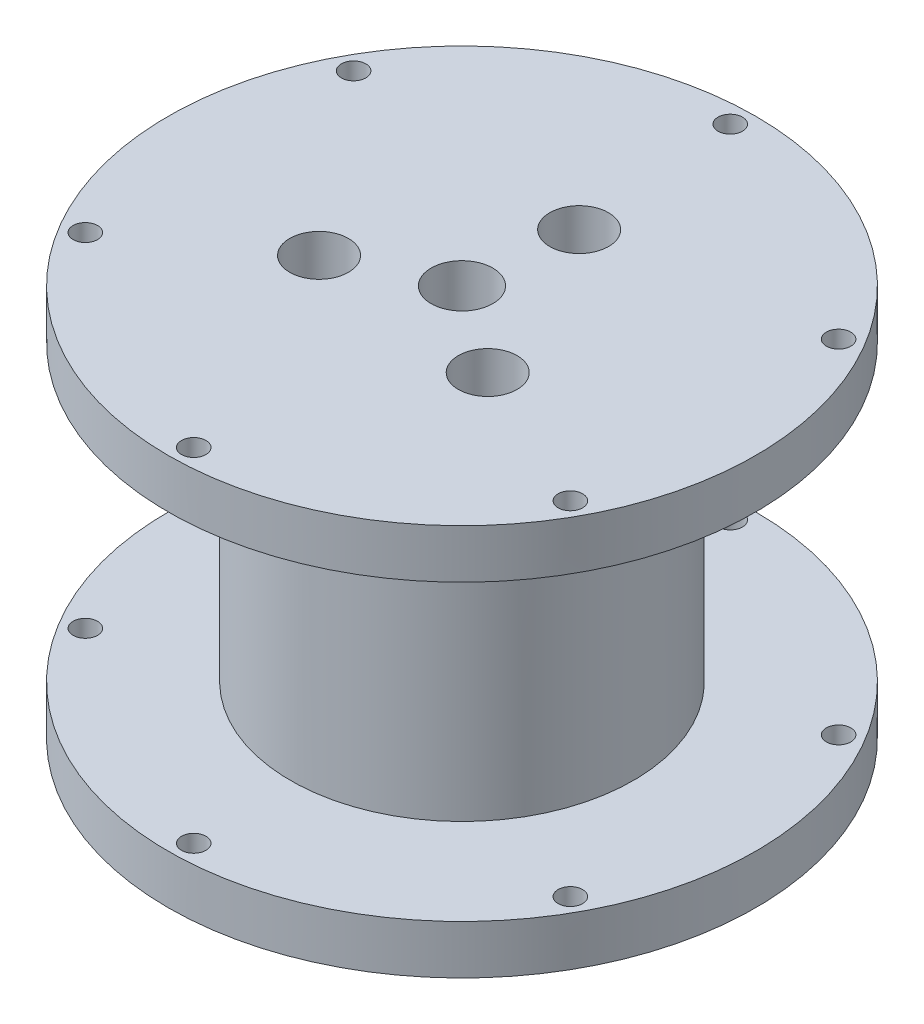
SolidWorks part; units mm, degrees
ref_plane "Front Plane" through (0, 0, 0) normal (0, 0, 1) x (1, 0, 0)
ref_plane "Top Plane" through (0, 0, 0) normal (0, 1, 0) x (1, 0, 0)
ref_plane "Right Plane" through (0, 0, 0) normal (1, 0, 0) x (0, 0, -1)
sketch "Sketch1" plane through (0, 0, 0) normal (0, 1, 0) x (1, 0, 0)
  circle A0 centre (0, 0) radius 30
extrude "Boss-Extrude1" add sketch "Sketch1" along normal blind 40
sketch "Sketch2" plane through (0, 0, 0) normal (0, -1, 0) x (1, 0, 0)
  circle A1 centre (0, 0) radius 17.5
extrude "Cut-Extrude1" cut sketch "Sketch2" against normal blind 30 from offset 5 flip side to cut offset against normal yes
sketch "Sketch3" plane through (0, 0, 0) normal (0, -1, 0) x (1, 0, 0)
  circle A0 centre (0, 0) radius 3.15
  dimension "D1" = 6.3
extrude "Cut-Extrude2" cut sketch "Sketch3" against normal through all
sketch "Sketch4" plane through (0, 0, 0) normal (0, -1, 0) x (1, 0, 0)
  line L1 (-17.9618, -12.7033) -> (19.9823, -9.2037)
  line L2 (19.9823, -9.2037) -> (-2.0205, 21.907)
  line L3 (-2.0205, 21.907) -> (-17.9618, -12.7033)
  circle A0 centre (0, 0) radius 11 construction
  circle A1 centre (8.9809, 6.3517) radius 3
  circle A2 centre (1.0103, -10.9535) radius 3
  circle A3 centre (-9.9911, 4.6019) radius 3
  point P1 (8.9809, 6.3517)
  point P7 (1.0103, -10.9535)
  point P8 (-9.9911, 4.6019)
  dimension "D1" = 6
  dimension "D2" = 6
  dimension "D3" = 6
  dimension "D4" = 22
extrude "Cut-Extrude3" cut sketch "Sketch4" against normal through all contours L1 A2 | L1 A2 | L2 A1 | L2 A1 | L3 A3 | L3 A3 region at (0.8933, 0, -9.6857) region at (1.1272, 0, -12.2214) region at (-11.1476, 0, 5.1345) region at (-8.8347, 0, 4.0692) region at (7.9414, 0, 5.6165) region at (10.0204, 0, 7.0869)
sketch "Sketch5" plane through (0, 5, 0) normal (0, 1, 0) x (1, 0, 0)
  circle A0 centre (-15.3397, 8.4227) radius 2
  circle A1 centre (0, 0) radius 17.5 construction
extrude "Cut-Extrude4" cut sketch "Sketch5" against normal up to next from offset 3
sketch "Sketch6" plane through (0, 0, 0) normal (0, -1, 0) x (1, 0, 0)
  line L1 (-6.3112, -0.7086) -> (-2.5419, -5.82)
  line L2 (-2.5419, -5.82) -> (3.7693, -5.1113)
  line L3 (3.7693, -5.1113) -> (6.3112, 0.7086)
  line L4 (6.3112, 0.7086) -> (2.5419, 5.82)
  line L5 (2.5419, 5.82) -> (-3.7693, 5.1113)
  line L6 (-3.7693, 5.1113) -> (-6.3112, -0.7086)
  circle A0 centre (0, 0) radius 5.5 construction
  dimension "D1" = 11
extrude "Cut-Extrude5" cut sketch "Sketch6" against normal blind 7.5
fillet "Fillet1" radius 2 1 edges at (-13.5866, 8, -7.4601)
sketch "Sketch7" plane through (0, 0, 0) normal (0, -1, 0) x (-1, 0, 0)
  line L0 (15.3397, 8.4227) -> (0, 0) construction
  line L1 (0, 0) -> (-26.2967, -14.439) construction
  line L3 (-24.5436, -13.4764) -> (-0.6009, -27.9936)
  line L4 (-0.6009, -27.9936) -> (23.9427, -14.5172)
  line L5 (23.9427, -14.5172) -> (24.5436, 13.4764)
  line L6 (24.5436, 13.4764) -> (0.6009, 27.9936)
  line L7 (0.6009, 27.9936) -> (-23.9427, 14.5172)
  line L8 (-23.9427, 14.5172) -> (-24.5436, -13.4764)
  circle A0 centre (0, 0) radius 30 construction
  circle A1 centre (-24.5436, -13.4764) radius 1.25
  circle A2 centre (0, 0) radius 24.2487 construction
  circle A3 centre (-0.6009, -27.9936) radius 1.25
  circle A4 centre (23.9427, -14.5172) radius 1.25
  circle A5 centre (24.5436, 13.4764) radius 1.25
  circle A6 centre (0.6009, 27.9936) radius 1.25
  circle A7 centre (-23.9427, 14.5172) radius 1.25
  dimension "D1" = 2
  dimension "D2" = 2.5
  dimension "D3" = 2.5
  dimension "D4" = 2.5
  dimension "D5" = 2.5
  dimension "D6" = 2.5
  dimension "D7" = 2.5
extrude "Cut-Extrude6" cut sketch "Sketch7" against normal through all both and the other way through all contours L3 A1 L8 | L8 A1 L3 | L4 A3 L3 | L3 A3 L4 | L5 A4 L4 | L4 A4 L5 | L6 A5 L5 | L5 A5 L6 | L6 A6 L7 | L7 A6 L6 | L7 A7 L8 | L8 A7 L7 region at (23.9395, 0, 13.1447) region at (24.8456, 0, 13.6422) region at (0.5861, 0, 27.3045) region at (0.6083, 0, 28.3381) region at (24.2373, 0, -14.6958) region at (23.3534, 0, -14.1599) region at (-23.3534, 0, 14.1599) region at (-24.2373, 0, 14.6958) region at (-0.6083, 0, -28.3381) region at (-0.5861, 0, -27.3045) region at (-23.9395, 0, -13.1447) region at (-24.8456, 0, -13.6422)
